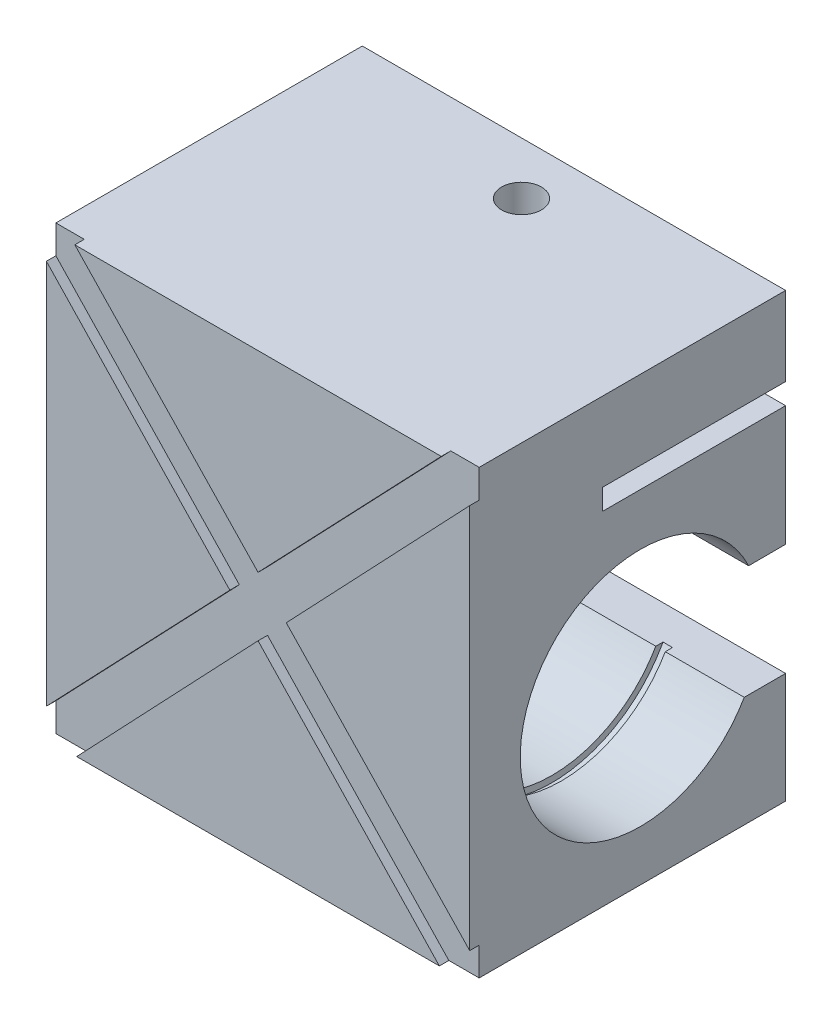
SolidWorks part; units mm, degrees
material "AISI 1020"
ref_plane "Front Plane" through (0, 0, 0) normal (0, 0, 1) x (1, 0, 0)
ref_plane "Top Plane" through (0, 0, 0) normal (0, 1, 0) x (1, 0, 0)
ref_plane "Right Plane" through (0, 0, 0) normal (1, 0, 0) x (0, 0, -1)
sketch "Sketch1" plane through (0, 0, 0) normal (0, 0, 1) x (1, 0, 0)
  line L0 (-33.5, -30.5) -> (-4.467, -0.0734)
  line L1 (33.5, -35) -> (-33.5, -35)
  line L2 (33.5, -35) -> (33.5, 35)
  line L3 (33.5, 35) -> (-33.5, 35)
  line L4 (-33.5, -35) -> (-33.5, 35)
  line L5 (0, 4.608) -> (-29, 35)
  line L7 (33.5, 30.5) -> (4.467, -0.0734)
  line L8 (0, -55) -> (0, 55) construction
  line L9 (-33.5, 30.5) -> (-4.467, -0.0734)
  line L10 (33.5, -30.5) -> (4.467, -0.0734)
  line L11 (0, -4.7773) -> (-28.7, -35)
  line L13 (0, 4.608) -> (29, 35)
  line L14 (0, -4.7773) -> (28.7, -35)
  point P0 (0, 0)
  point P5 (28.7, -35)
  point P6 (-33.5, -35)
  point P8 (-28.7, -35)
  point P9 (-33.5, -30.5)
  point P10 (33.5, -30.5)
  point P11 (33.5, 30.5)
  point P12 (33.5, -44.7357)
  point P13 (38.6848, 35)
  point P14 (29, 35)
extrude "Boss-Extrude1" add sketch "Sketch1" against normal blind 50 contours L5 L13 L3 | L9 L4 L0 | L14 L11 L1 | L10 L2 L7 | L11 L14 L1 L2 L10 L7 L3 L13 L5 L4 L9 L0 region at (-23.8223, -0.0245, 0) region at (0, -0.2182, 0) region at (0, -24.9258, 0) region at (0, 24.8693, 0) region at (23.8223, -0.0245, 0)
ref_plane "Plane1" through (0, 35, 0) normal (0, 1, 0) x (1, 0, 0)
sketch "Sketch5" plane through (0, 35, 0) normal (0, 1, 0) x (1, 0, 0)
  circle A0 centre (0, 41.7) radius 3.15
  point P0 (-31.6029, 53.4321)
  point P1 (0, 41.7)
extrude "Cut-Extrude2" cut sketch "Sketch5" against normal blind 12.5
extrude "Cut-Extrude3" cut sketch "Sketch1<4>" against normal blind 1.5 contours L11 L14 L1 L2 L10 L7 L3 L13 L5 L4 L9 L0 region at (0, -0.2182, 0)
sketch "Sketch1<4>" plane through (0, 0, 0) normal (0, 0, 1) x (1, 0, 0) same geometry as "Sketch1"
ref_plane "Plane2" through (33.5, 0, 0) normal (1, 0, 0) x (0, 0, -1)
sketch "Sketch6" plane through (33.5, 0, 0) normal (1, 0, 0) x (0, 0, -1)
  line L0 (50, -35) -> (50, 35) construction
  line L1 (0, -35) -> (0, 35) construction
  line L2 (21, 22.5) -> (50, 22.5)
  line L3 (21, 22.5) -> (21, 19.2)
  line L4 (21, 19.2) -> (50, 19.2)
  line L5 (50, 22.5) -> (50, 19.2)
  line L6 (50, -35) -> (1.5, -35) construction
  line L7 (50, 0.2) -> (44.1506, 0.1766)
  line L8 (50, -17.5) -> (43.4545, -17.5)
  line L9 (50, 0.2) -> (50, -17.5)
  arc A0 (44.1506, 0.1766) -> (43.4545, -17.5) centre (27, -8) ccw
  point P0 (50, 22.5)
  point P1 (50, 19.2)
  point P4 (21, 22.5)
  point P5 (21, 19.2)
  point P10 (50, 0.2)
  point P11 (0, -8)
  point P12 (27, -35)
  point P15 (27, -8)
  point P21 (50, -17.5)
extrude "Cut-Extrude4" cut sketch "Sketch6" against normal blind 67
ref_plane "Plane3" through (21, 0, 0) normal (1, 0, 0) x (0, 0, -1)
sketch "Sketch7" plane through (21, 0, 0) normal (1, 0, 0) x (0, 0, -1)
  line L0 (0, -35) -> (0, 35) construction
  line L1 (50, -35) -> (1.5, -35) construction
  circle A0 centre (27, -8) radius 20
  point P0 (0, -8)
  point P1 (27, -35)
  point P4 (27, -8)
extrude "Cut-Extrude5" cut sketch "Sketch7" against normal blind 1.5
ref_plane "Plane4" through (-22.5, 0, 0) normal (1, 0, 0) x (0, 0, -1)
sketch "Sketch8" plane through (-22.5, 0, 0) normal (1, 0, 0) x (0, 0, -1)
  line L0 (0, -35) -> (0, 35) construction
  circle A0 centre (27, -8) radius 20
  point P0 (0, -8)
extrude "Cut-Extrude6" cut sketch "Sketch8" against normal blind 1.5
